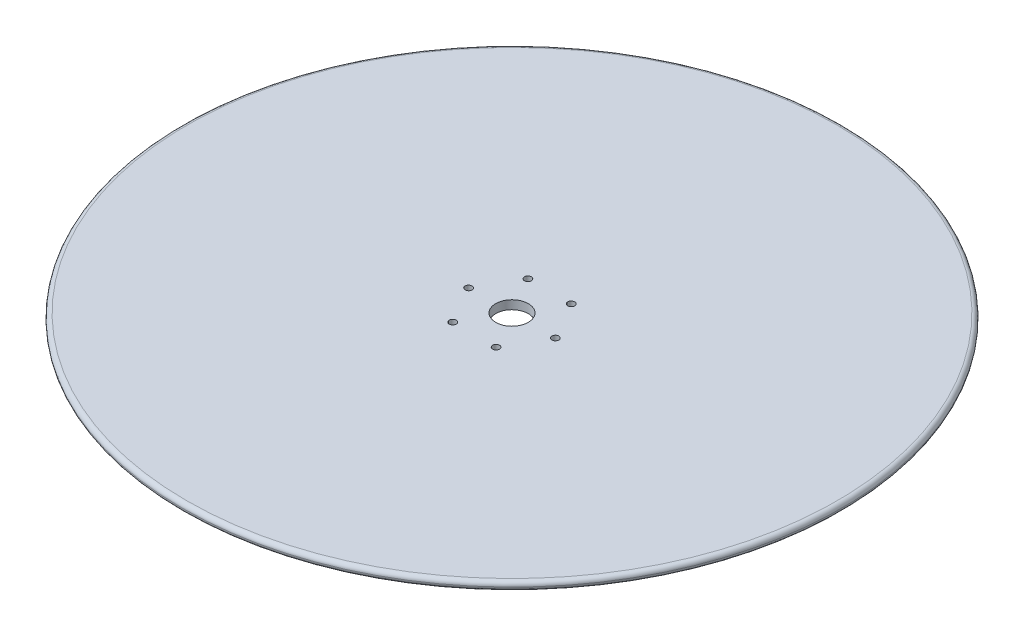
SolidWorks part; units mm, degrees
material "6061-T6 (SS)"
ref_plane "Alzado" through (0, 0, 0) normal (0, 0, 1) x (1, 0, 0)
ref_plane "Planta" through (0, 0, 0) normal (0, 1, 0) x (1, 0, 0)
ref_plane "Vista lateral" through (0, 0, 0) normal (1, 0, 0) x (0, 0, -1)
sketch "Croquis1" plane through (0, 0, 0) normal (0, 1, 0) x (1, 0, 0)
  circle A0 centre (0, 0) radius 380
  circle A1 centre (0, 0) radius 18.75
  dimension "D1" = 760
  dimension "D2" = 37.5
extrude "Saliente-Extruir1" add sketch "Croquis1" along normal blind 10
sketch "Croquis2" plane through (0, 10, 0) normal (0, 1, 0) x (1, 0, 0)
  line L0 (0, 0) -> (-329.0897, -190) construction
  line L1 (50, 0) -> (25, 43.3013) construction
  line L2 (25, 43.3013) -> (-25, 43.3013) construction
  line L3 (-25, 43.3013) -> (-50, 0) construction
  line L4 (-50, 0) -> (-25, -43.3013) construction
  line L5 (-25, -43.3013) -> (25, -43.3013) construction
  line L6 (25, -43.3013) -> (50, 0) construction
  line L7 (0, 0) -> (329.0897, -190) construction
  line L8 (0, 0) -> (0, 380) construction
  line L9 (0, 0) -> (-25, -43.3013) construction
  circle A0 centre (0, 0) radius 43.3013 construction
  circle A1 centre (0, 0) radius 380 construction
  circle A2 centre (-25, -43.3013) radius 4
  circle A3 centre (-50, 0) radius 4
  circle A4 centre (-25, 43.3013) radius 4
  circle A5 centre (25, 43.3013) radius 4
  circle A6 centre (50, 0) radius 4
  circle A7 centre (25, -43.3013) radius 4
  dimension "D4" = 8
  dimension "D5" = 6
  dimension "D1" = 50
  dimension "D2" = 120
  dimension "D3" = 120
  dimension "D6" = 50
extrude "Cortar-Extruir1" cut sketch "Croquis2" against normal through all
fillet "Redondeo1" radius 5 2 edges at (0, 0, 380) (0, 10, 380)
